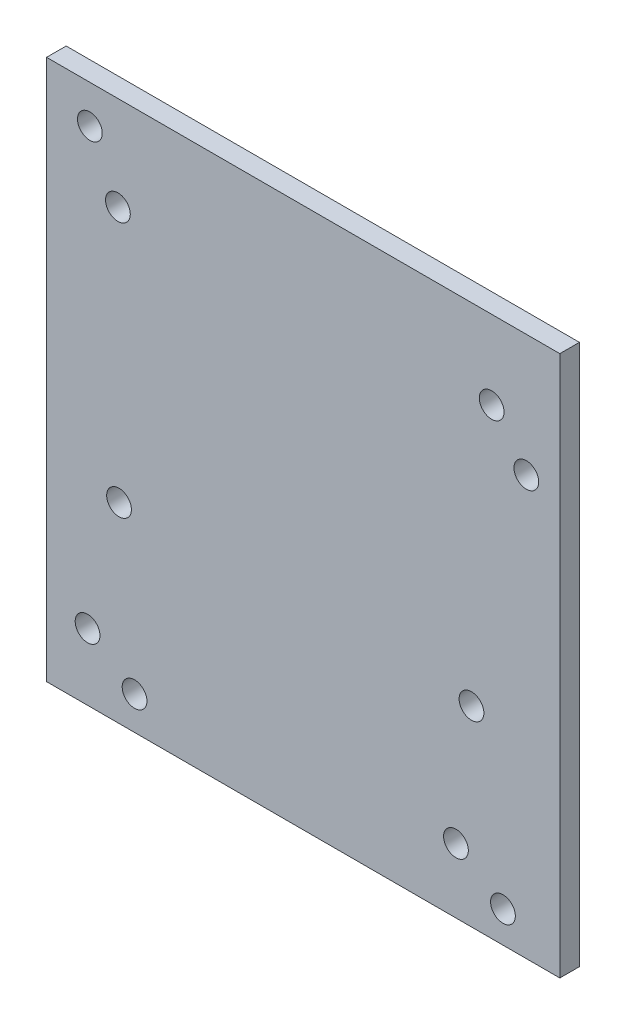
SolidWorks part; units mm, degrees
ref_plane "Front Plane" through (0, 0, 0) normal (0, 0, 1) x (1, 0, 0)
ref_plane "Top Plane" through (0, 0, 0) normal (0, 1, 0) x (1, 0, 0)
ref_plane "Right Plane" through (0, 0, 0) normal (1, 0, 0) x (0, 0, -1)
sketch "Sketch1" plane through (0, 0, 0) normal (0, 0, 1) x (1, 0, 0)
  line L0 (-570.3819, 236.4783) -> (-570.3819, 211.0783) construction
  line L5 (-570.3819, 211.0783) -> (-540.0489, 211.0783) construction
  line L6 (-540.0489, 211.0783) -> (-540.0489, 236.4783) construction
  line L7 (-540.0489, 236.4783) -> (-570.3819, 236.4783) construction
  line L8 (-532.8862, 362.9134) -> (-560.1463, 365.8966) construction
  line L9 (-560.1463, 365.8966) -> (-560.5461, 336.3644) construction
  line L10 (-560.5461, 336.3644) -> (-533.286, 333.3813) construction
  line L11 (-533.286, 333.3813) -> (-532.8862, 362.9134) construction
  line L12 (-659.3105, 377.0773) -> (-686.7338, 380.0783) construction
  line L13 (-686.7338, 380.0783) -> (-692.9825, 350.529) construction
  line L14 (-692.9825, 350.529) -> (-665.5591, 347.5279) construction
  line L15 (-665.5591, 347.5279) -> (-659.3105, 377.0773) construction
  line L16 (-660.6408, 211.0783) -> (-660.6408, 236.4783) construction
  line L17 (-660.6408, 236.4783) -> (-690.9738, 236.4783) construction
  line L18 (-690.9738, 236.4783) -> (-690.9738, 211.0783) construction
  line L19 (-690.9738, 211.0783) -> (-660.6408, 211.0783) construction
  line L20 (-570.3819, 236.4783) -> (-570.3819, 211.0783) construction
  line L21 (-570.3819, 211.0783) -> (-540.0489, 211.0783) construction
  line L22 (-540.0489, 211.0783) -> (-540.0489, 236.4783) construction
  line L23 (-540.0489, 236.4783) -> (-570.3819, 236.4783) construction
  line L24 (-532.8862, 362.9134) -> (-560.1463, 365.8966) construction
  line L25 (-560.1463, 365.8966) -> (-560.5461, 336.3644) construction
  line L26 (-560.5461, 336.3644) -> (-533.286, 333.3813) construction
  line L27 (-533.286, 333.3813) -> (-532.8862, 362.9134) construction
  line L28 (-659.3105, 377.0773) -> (-686.7338, 380.0783) construction
  line L29 (-686.7338, 380.0783) -> (-692.9825, 350.529) construction
  line L30 (-692.9825, 350.529) -> (-665.5591, 347.5279) construction
  line L31 (-665.5591, 347.5279) -> (-659.3105, 377.0773) construction
  line L32 (-660.6408, 211.0783) -> (-660.6408, 236.4783) construction
  line L33 (-660.6408, 236.4783) -> (-690.9738, 236.4783) construction
  line L34 (-690.9738, 236.4783) -> (-690.9738, 211.0783) construction
  line L35 (-690.9738, 211.0783) -> (-660.6408, 211.0783) construction
  line L36 (-686.7338, 380.0783) -> (-540.0489, 211.0783) construction
  line L37 (-690.9738, 211.0783) -> (-532.8862, 362.9134) construction
  line L39 (-696.1575, 207.9033) -> (-529.7112, 207.9033)
  line L40 (-696.1575, 207.9033) -> (-696.1575, 383.2533)
  line L41 (-696.1575, 383.2533) -> (-529.7112, 383.2533)
  line L42 (-529.7112, 207.9033) -> (-529.7112, 383.2533)
  line L43 (-696.1575, 207.9033) -> (-529.7112, 383.2533) construction
  line L44 (-696.1575, 383.2533) -> (-529.7112, 207.9033) construction
  circle A0 centre (-548.1569, 218.0633) radius 2.5273 construction
  circle A1 centre (-563.3969, 228.8583) radius 2.5273 construction
  circle A2 centre (-540.573, 343.7606) radius 2.5273 construction
  circle A3 centre (-551.816, 357.7668) radius 2.5273 construction
  circle A4 centre (-673.0254, 352.7515) radius 2.5273 construction
  circle A5 centre (-682.1218, 370.9328) radius 2.5273 construction
  circle A6 centre (-682.8658, 229.4933) radius 2.5273 construction
  circle A7 centre (-667.6258, 218.6983) radius 2.5273 construction
  circle A8 centre (-548.1569, 218.0633) radius 2.5273 construction
  circle A9 centre (-563.3969, 228.8583) radius 2.5273 construction
  circle A10 centre (-540.573, 343.7606) radius 2.5273 construction
  circle A11 centre (-551.816, 357.7668) radius 2.5273 construction
  circle A12 centre (-673.0254, 352.7515) radius 2.5273 construction
  circle A13 centre (-682.1218, 370.9328) radius 2.5273 construction
  circle A14 centre (-682.8658, 229.4933) radius 2.5273 construction
  circle A15 centre (-667.6258, 218.6983) radius 2.5273 construction
  circle A23 centre (-667.6258, 218.6983) radius 4.0127
  circle A24 centre (-682.8658, 229.4933) radius 4.0127
  circle A25 centre (-682.1218, 370.9328) radius 4.0127
  circle A26 centre (-673.0254, 352.7515) radius 4.0127
  circle A27 centre (-551.816, 357.7668) radius 4.0127
  circle A28 centre (-540.573, 343.7606) radius 4.0127
  circle A29 centre (-548.1569, 218.0633) radius 4.0127
  circle A30 centre (-563.3969, 228.8583) radius 4.0127
  circle A31 centre (-558.3616, 269.9726) radius 3 construction
  circle A32 centre (-672.6612, 269.9726) radius 3 construction
  circle A33 centre (-558.3616, 269.9726) radius 3 construction
  circle A34 centre (-672.6612, 269.9726) radius 3 construction
  circle A35 centre (-558.3616, 269.9726) radius 4.0132
  circle A36 centre (-672.6612, 269.9726) radius 4.0132
  point P1 (-608.6645, 290.1323)
  point P18 (-612.9344, 295.5783)
  dimension "D5" = 8.0254
  dimension "D6" = 8.0264
  dimension "D1" = 3.175
  dimension "D2" = 3.175
  dimension "D3" = 3.175
  dimension "D4" = 3.175
extrude "Boss-Extrude1" add sketch "Sketch1" along normal blind 6.35
